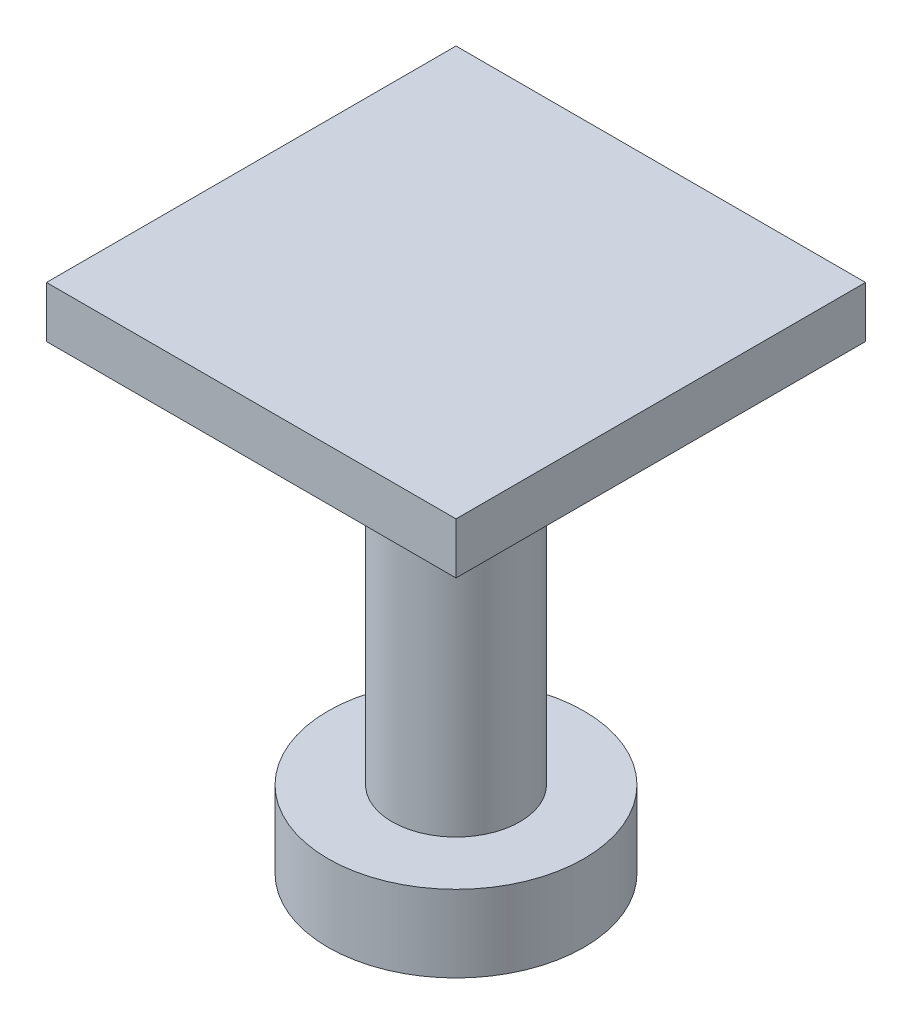
SolidWorks part; units mm, degrees
ref_plane "Спереди" through (0, 0, 0) normal (0, 0, 1) x (1, 0, 0)
ref_plane "Сверху" through (0, 0, 0) normal (0, 1, 0) x (1, 0, 0)
ref_plane "Справа" through (0, 0, 0) normal (1, 0, 0) x (0, 0, -1)
sketch "Эскиз1" plane through (0, 0, 0) normal (0, 0, 1) x (1, 0, 0)
  line L0 (0, 0) -> (-25, 0)
  line L1 (-25, 0) -> (-25, 15)
  line L2 (-25, 15) -> (-12.5, 15)
  line L3 (-12.5, 15) -> (-12.5, 90)
  line L4 (-12.5, 90) -> (-40, 90)
  line L5 (-40, 90) -> (-40, 100)
  line L6 (-40, 100) -> (0, 100)
  line L7 (0, 100) -> (0, 0)
  line L8 (0, 0) -> (0, -3.8483) construction
  dimension "D1" = 100
  dimension "D2" = 50
  dimension "D3" = 25
  dimension "D4" = 15
  dimension "D5" = 40
  dimension "D6" = 10
revolve "Повернуть1" add sketch "Эскиз1" angle 360 about L8
sketch "Эскиз2" plane through (0, 100, 0) normal (0, 1, 0) x (1, 0, 0)
  line L1 (-40, -40) -> (40, -40)
  line L2 (-40, -40) -> (-40, 40)
  line L3 (-40, 40) -> (40, 40)
  line L4 (40, -40) -> (40, 40)
  line L5 (-40, -40) -> (40, 40) construction
  line L6 (-40, 40) -> (40, -40) construction
  circle A0 centre (0, 0) radius 40 construction
  point P0 (0, 0)
extrude "Бобышка-Вытянуть1" add sketch "Эскиз2" against normal up to surface (10 mm away) up to face at (0, 90, 12.5)
